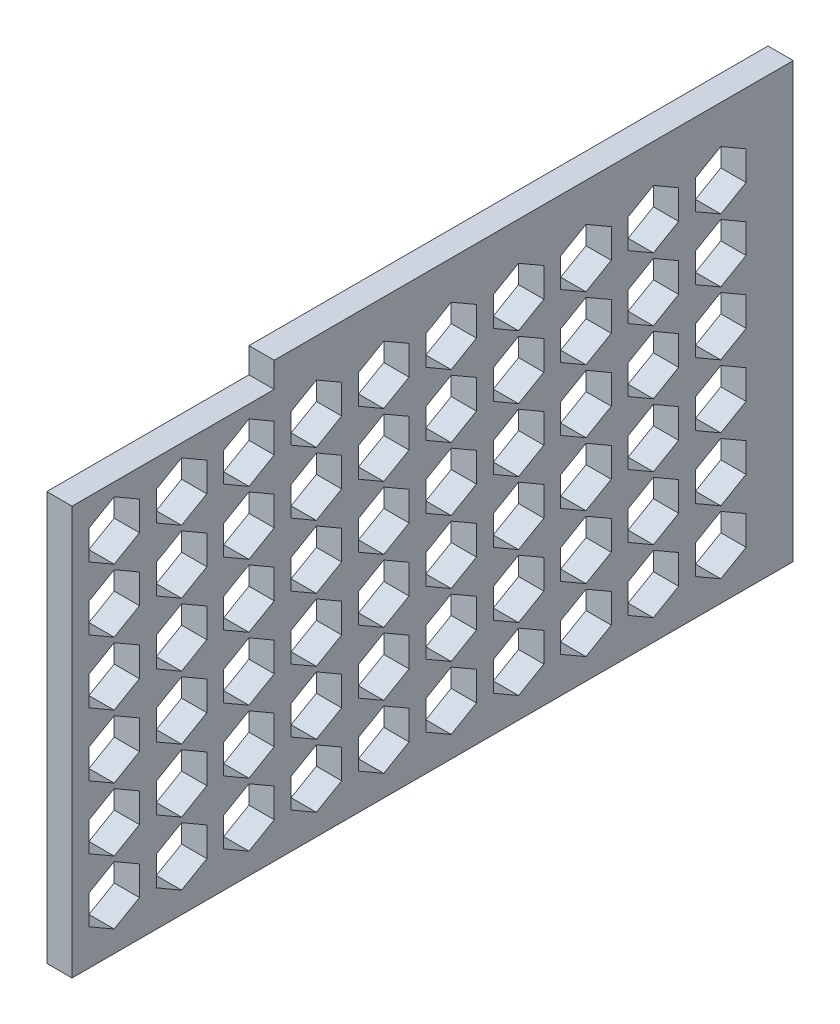
SolidWorks part; units mm, degrees
material "ABS"
ref_plane "前视基准面" through (0, 0, 0) normal (0, 0, 1) x (1, 0, 0)
ref_plane "上视基准面" through (0, 0, 0) normal (0, 1, 0) x (1, 0, 0)
ref_plane "右视基准面" through (0, 0, 0) normal (1, 0, 0) x (0, 0, -1)
other "Configuration Table"
sketch "草图1" plane through (0, 0, 0) normal (1, 0, 0) x (0, 0, -1)
  line L0 (0, 0) -> (24, 0)
  line L1 (24, 0) -> (24, 3)
  line L2 (24, 3) -> (85.6, 3)
  line L3 (85.6, 3) -> (85.6, -48.5)
  line L4 (85.6, -48.5) -> (0, -48.5)
  line L5 (0, -48.5) -> (0, 0)
  dimension "D1" = 24
  dimension "D2" = 61.6
  dimension "D3" = 51.5
extrude "凸台-拉伸1" add sketch "草图1" along normal blind 3
sketch "草图2" plane through (3, 0, 0) normal (1, 0, 0) x (0, 0, -1)
  line L0 (0, 0) -> (0, -5)
  line L1 (0, 0) -> (0, -48.5) construction
  line L2 (0, -5) -> (5, -5)
  line L3 (0, -48.5) -> (5, -48.5)
  line L4 (0, -48.5) -> (85.6, -48.5) construction
  line L5 (5, -48.5) -> (5, -43.5)
  line L6 (5, -43.5) -> (5, -5)
  line L7 (85.6, -48.5) -> (85.6, -43.5)
  line L8 (85.6, -48.5) -> (85.6, 3) construction
  line L9 (85.6, -43.5) -> (80.6, -43.5)
  line L10 (5, -5) -> (80.6, -5)
  line L11 (80.6, -5) -> (80.6, -43.5)
  line L12 (5, -43.5) -> (80.6, -43.5)
  line L13 (5, -5) -> (8, -5)
  line L14 (5, -8.4641) -> (8, -6.7321)
  line L15 (8, -6.7321) -> (8, -3.2679)
  line L16 (8, -3.2679) -> (5, -1.5359)
  line L17 (5, -1.5359) -> (2, -3.2679)
  line L18 (2, -3.2679) -> (2, -6.7321)
  line L19 (2, -6.7321) -> (5, -8.4641)
  line L20 (8, -5) -> (10, -5)
  line L21 (10, -5) -> (13, -5)
  line L22 (5, -5) -> (5, -11)
  line L23 (13, -8.4641) -> (16, -6.7321)
  line L24 (16, -6.7321) -> (16, -3.2679)
  line L25 (16, -3.2679) -> (13, -1.5359)
  line L26 (13, -1.5359) -> (10, -3.2679)
  line L27 (10, -3.2679) -> (10, -6.7321)
  line L28 (10, -6.7321) -> (13, -8.4641)
  circle A0 centre (5, -5) radius 3 construction
  circle A1 centre (13, -5) radius 3 construction
  dimension "D1" = 2
  dimension "D2" = 3
extrude "切除-拉伸1" cut sketch "草图2" against normal blind 3 contours L27 L28 L23 L24 L10 | L14 L15 L10 L6 | L17 L18 L2 L10 L15 L16 | L18 L19 L6 L2 | L26 L27 L10 L24 L25 region at (3, -3.6528, -5) region at (3, -6.3472, -3.6667) region at (3, -6.3472, -6.3333) region at (3, -3.6528, -13) region at (3, -6.3472, -13)
pattern_linear "阵列(线性)1" count 5 spacing 16 along (0, 0, -1) of "切除-拉伸1"
pattern_linear "阵列(线性)2" count 6 spacing 7.5 along (0, -1, 0) of "切除-拉伸1", "阵列(线性)1"
